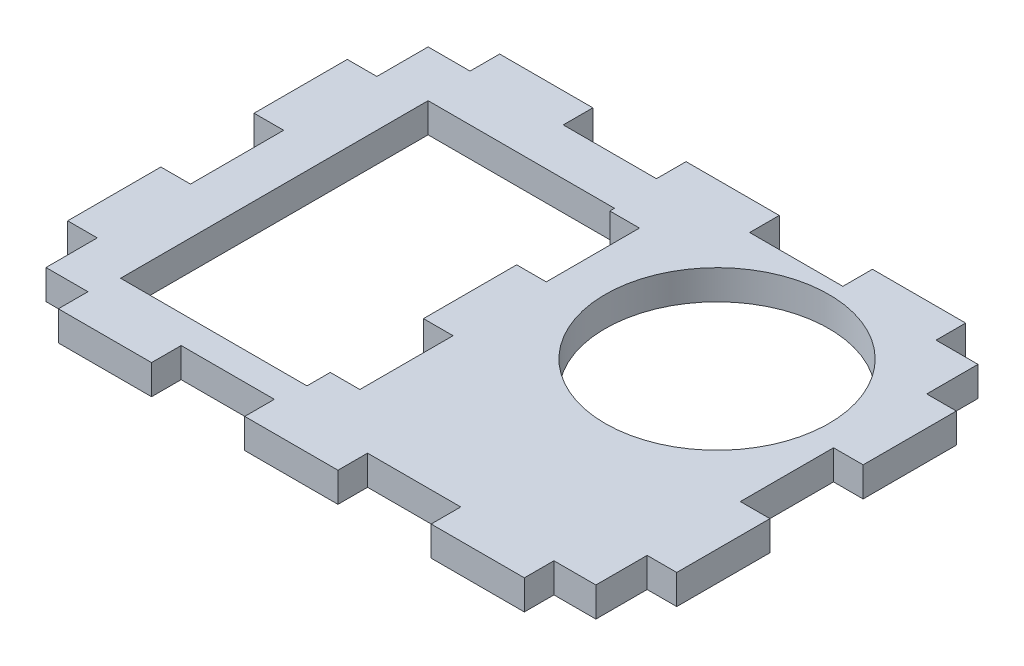
SolidWorks part; units mm, degrees
ref_plane "Front Plane" through (0, 0, 0) normal (0, 0, 1) x (1, 0, 0)
ref_plane "Top Plane" through (0, 0, 0) normal (0, 1, 0) x (1, 0, 0)
ref_plane "Right Plane" through (0, 0, 0) normal (1, 0, 0) x (0, 0, -1)
sketch "Sketch1" plane through (0, 0, 0) normal (0, 1, 0) x (1, 0, 0)
  line L1 (0, 0) -> (65.35, 0)
  line L2 (0, 0) -> (0, 47.35)
  line L3 (0, 47.35) -> (65.35, 47.35)
  line L4 (65.35, 0) -> (65.35, 47.35)
  line L5 (8.175, 6.175) -> (28.175, 6.175)
  line L6 (8.175, 6.175) -> (8.175, 39.175)
  line L7 (8.175, 39.175) -> (28.175, 39.175)
  line L8 (28.175, 6.175) -> (28.175, 39.175)
  circle A0 centre (47.675, 30.675) radius 12
  dimension "D7" = 24
  dimension "D1" = 47.35
  dimension "D2" = 65.35
  dimension "D3" = 8.175
  dimension "D4" = 6.175
  dimension "D5" = 8.175
  dimension "D6" = 20
  dimension "D8" = 17.675
  dimension "D9" = 16.675
extrude "Boss-Extrude1" add sketch "Sketch1" along normal blind 3.175
sketch "Sketch2" plane through (0, 3.175, 0) normal (0, 1, 0) x (1, 0, 0)
  line L0 (0, 47.35) -> (0, 0) construction
  line L1 (3.175, 8.675) -> (0, 8.675)
  line L2 (3.175, 8.675) -> (3.175, 0)
  line L3 (3.175, 0) -> (0, 0)
  line L4 (0, 8.675) -> (0, 0)
  line L5 (28.175, 6.175) -> (28.175, 39.175) construction
  line L6 (3.175, 18.675) -> (0, 18.675)
  line L7 (3.175, 18.675) -> (3.175, 28.675)
  line L8 (3.175, 28.675) -> (0, 28.675)
  line L9 (0, 18.675) -> (0, 28.675)
  line L10 (3.175, 38.675) -> (0, 38.675)
  line L11 (3.175, 38.675) -> (3.175, 47.35)
  line L12 (3.175, 47.35) -> (0, 47.35)
  line L13 (0, 38.675) -> (0, 47.35)
  line L14 (65.35, 47.35) -> (0, 47.35) construction
  line L15 (62.175, 38.675) -> (65.35, 38.675)
  line L16 (62.175, 38.675) -> (62.175, 47.35)
  line L17 (62.175, 47.35) -> (65.35, 47.35)
  line L18 (65.35, 38.675) -> (65.35, 47.35)
  line L19 (65.35, 0) -> (65.35, 47.35) construction
  line L20 (0, 0) -> (65.35, 0) construction
  line L21 (62.175, 28.675) -> (65.35, 28.675)
  line L22 (62.175, 28.675) -> (62.175, 18.675)
  line L23 (62.175, 18.675) -> (65.35, 18.675)
  line L24 (65.35, 28.675) -> (65.35, 18.675)
  line L25 (62.175, 8.675) -> (65.35, 8.675)
  line L26 (62.175, 8.675) -> (62.175, 0)
  line L27 (62.175, 0) -> (65.35, 0)
  line L28 (65.35, 8.675) -> (65.35, 0)
  line L29 (57.675, 3.175) -> (62.175, 3.175)
  line L30 (57.675, 3.175) -> (57.675, 0)
  line L31 (57.675, 0) -> (62.175, 0)
  line L32 (62.175, 3.175) -> (62.175, 0)
  line L33 (7.675, 3.175) -> (3.175, 3.175)
  line L34 (7.675, 3.175) -> (7.675, 0)
  line L35 (7.675, 0) -> (3.175, 0)
  line L36 (3.175, 3.175) -> (3.175, 0)
  line L37 (17.675, 3.175) -> (27.675, 3.175)
  line L38 (17.675, 3.175) -> (17.675, 0)
  line L39 (17.675, 0) -> (27.675, 0)
  line L40 (27.675, 3.175) -> (27.675, 0)
  line L41 (65.35, 47.35) -> (0, 47.35) construction
  line L42 (37.675, 3.175) -> (47.675, 3.175)
  line L43 (37.675, 3.175) -> (37.675, 0)
  line L44 (37.675, 0) -> (47.675, 0)
  line L45 (47.675, 3.175) -> (47.675, 0)
  line L46 (47.675, 44.175) -> (37.675, 44.175)
  line L47 (47.675, 44.175) -> (47.675, 47.35)
  line L48 (47.675, 47.35) -> (37.675, 47.35)
  line L49 (37.675, 44.175) -> (37.675, 47.35)
  line L50 (57.675, 44.175) -> (62.175, 44.175)
  line L51 (57.675, 44.175) -> (57.675, 47.35)
  line L52 (57.675, 47.35) -> (62.175, 47.35)
  line L53 (62.175, 44.175) -> (62.175, 47.35)
  line L54 (27.675, 44.175) -> (17.675, 44.175)
  line L55 (27.675, 44.175) -> (27.675, 47.35)
  line L56 (27.675, 47.35) -> (17.675, 47.35)
  line L57 (17.675, 44.175) -> (17.675, 47.35)
  line L58 (7.675, 44.175) -> (0, 44.175)
  line L59 (7.675, 44.175) -> (7.675, 47.35)
  line L60 (7.675, 47.35) -> (0, 47.35)
  line L61 (0, 44.175) -> (0, 47.35)
  line L62 (31.35, 28.675) -> (28.175, 28.675)
  line L63 (31.35, 28.675) -> (31.35, 38.675)
  line L64 (31.35, 38.675) -> (28.175, 38.675)
  line L65 (28.175, 28.675) -> (28.175, 38.675)
  line L67 (31.35, 18.675) -> (28.175, 18.675)
  line L68 (31.35, 18.675) -> (31.35, 8.675)
  line L69 (31.35, 8.675) -> (28.175, 8.675)
  line L70 (28.175, 18.675) -> (28.175, 8.675)
  line M1 (0, 47.35) -> (0, 0)
  line M2 (0, 0) -> (65.35, 0)
  line M3 (65.35, 0) -> (65.35, 47.35)
  line M4 (65.35, 47.35) -> (0, 47.35)
  line M7 (28.175, 39.175) -> (28.175, 6.175)
  dimension "D1" = 10
  dimension "D2" = 8.675
  dimension "D3" = 3.175
  dimension "D4" = 10
  dimension "D5" = 10
  dimension "D6" = 3.175
  dimension "D7" = 10
  dimension "D8" = 10
  dimension "D9" = 10
  dimension "D10" = 4.5
  dimension "D11" = 10
extrude "Cut-Extrude1" cut sketch "Sketch2" against normal blind 3.175 contours L57 L54 L55 M4 | L49 L46 L47 M4 | L51 L50 L16 M4 | L16 L15 M3 M4 | L22 L23 L21 M3 | L25 L26 M2 M3 | L29 L30 L26 M2 | L45 L42 L43 M2 | L40 L37 L38 M2 | L34 L33 L2 M2 | L2 L1 M1 M2 | L7 L8 L6 M1 | L11 L58 L13 L10 | L58 L59 L11 M4 | L58 L11 M4 M1 | L63 L64 L62 M7 | L69 L68 L67 M7 region at (1.5875, 3.175, -4.3375) region at (5.425, 3.175, -1.5875) region at (1.5875, 3.175, -23.675) region at (1.5875, 3.175, -41.425) region at (22.675, 3.175, -1.5875) region at (1.5875, 3.175, -45.7625) region at (5.425, 3.175, -45.7625) region at (42.675, 3.175, -1.5875) region at (59.925, 3.175, -1.5875) region at (22.675, 3.175, -45.7625) region at (63.7625, 3.175, -4.3375) region at (42.675, 3.175, -45.7625) region at (63.7625, 3.175, -23.675) region at (59.925, 3.175, -45.7625) region at (63.7625, 3.175, -43.0125) region at (29.7625, 3.175, -13.675) region at (29.7625, 3.175, -33.675)
